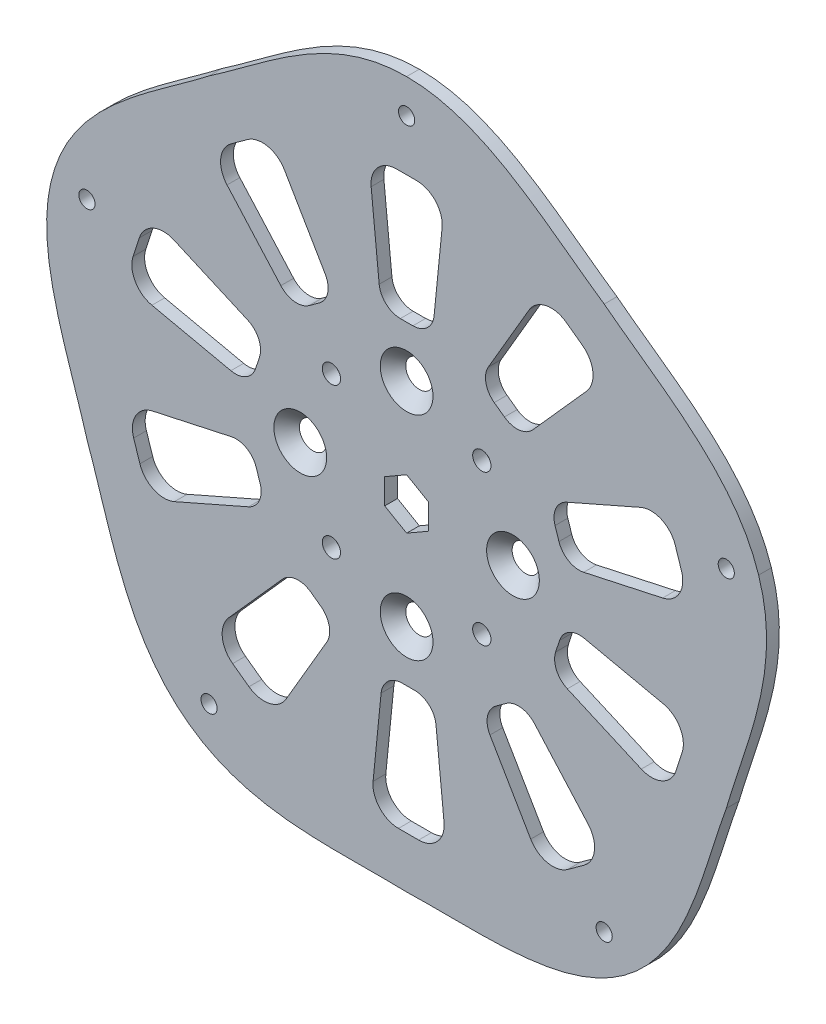
SolidWorks part; units mm, degrees
material "ABS"
ref_plane "Płaszczyzna przednia" through (0, 0, 0) normal (0, 0, 1) x (1, 0, 0)
ref_plane "Płaszczyzna górna" through (0, 0, 0) normal (0, 1, 0) x (1, 0, 0)
ref_plane "Płaszczyzna prawa" through (0, 0, 0) normal (1, 0, 0) x (0, 0, -1)
sketch "Szkic1" plane through (0, 0, 0) normal (0, 0, 1) x (1, 0, 0)
  line L0 (0, 0) -> (51.1373, 70.3845) construction
  line L1 (0, 0) -> (0, 87) construction
  line L2 (-1.4751, 37) -> (1.4751, 37)
  line L3 (-2.3701, 67) -> (2.3701, 67)
  line L4 (-6.4502, 41.5025) -> (-8.3403, 60.403)
  line L5 (6.4502, 41.5025) -> (8.3403, 60.403)
  line L6 (29.6563, 29.9183) -> (42.2948, 44.0981)
  line L7 (37.5075, 55.7306) -> (41.3424, 52.9445)
  line L8 (19.2195, 37.501) -> (28.7999, 53.9028)
  line L9 (20.5981, 30.9341) -> (22.9848, 29.2)
  line L10 (41.6213, 6.9063) -> (60.1808, 10.9493)
  line L11 (63.1452, 23.1741) -> (64.61, 18.6659)
  line L12 (37.6348, 19.1754) -> (55.0262, 26.8135)
  line L13 (34.8901, 13.0524) -> (35.8017, 10.2466)
  line L14 (37.7751, -18.7437) -> (55.1665, -26.3818)
  line L15 (64.7503, -18.2342) -> (63.2855, -22.7424)
  line L16 (41.7616, -6.4746) -> (60.321, -10.5176)
  line L17 (35.942, -9.8149) -> (35.0304, -12.6206)
  line L18 (19.5868, -37.2342) -> (29.1671, -53.6359)
  line L19 (41.7096, -52.6776) -> (37.8748, -55.4638)
  line L20 (30.0235, -29.6514) -> (42.662, -43.8313)
  line L21 (23.352, -28.9332) -> (20.9653, -30.6672)
  line L22 (-5.9963, -41.5025) -> (-7.8864, -60.403)
  line L23 (2.824, -67) -> (-1.9161, -67)
  line L24 (6.9042, -41.5025) -> (8.7942, -60.403)
  line L25 (1.929, -37) -> (-1.0211, -37)
  line L26 (-29.2023, -29.9183) -> (-41.8408, -44.0981)
  line L27 (-37.0536, -55.7306) -> (-40.8884, -52.9445)
  line L28 (-18.7656, -37.501) -> (-28.3459, -53.9028)
  line L29 (-20.1441, -30.9341) -> (-22.5308, -29.2)
  line L30 (-41.1673, -6.9063) -> (-59.7268, -10.9493)
  line L31 (-62.6913, -23.1741) -> (-64.1561, -18.6659)
  line L32 (-37.1809, -19.1754) -> (-54.5722, -26.8135)
  line L33 (-34.4362, -13.0524) -> (-35.3478, -10.2466)
  line L34 (-37.3211, 18.7437) -> (-54.7125, 26.3818)
  line L35 (-64.2963, 18.2342) -> (-62.8316, 22.7424)
  line L36 (-41.3076, 6.4746) -> (-59.8671, 10.5176)
  line L37 (-35.4881, 9.8149) -> (-34.5764, 12.6206)
  line L38 (-19.1328, 37.2342) -> (-28.7132, 53.6359)
  line L39 (-41.2557, 52.6776) -> (-37.4208, 55.4638)
  line L40 (-29.5696, 29.6514) -> (-42.2081, 43.8313)
  line L41 (-22.8981, 28.9332) -> (-20.5114, 30.6672)
  circle A0 centre (0, 0) radius 79 construction
  circle A2 centre (0, 0) radius 25 construction
  circle A3 centre (0, 0) radius 3.3
  circle A4 centre (0, 25) radius 3.2
  circle A5 centre (0, 79) radius 1.9
  circle A6 centre (25, 0) radius 3.2
  circle A7 centre (0, -25) radius 3.2
  circle A8 centre (-25, 0) radius 3.2
  circle A9 centre (75.1335, 24.4123) radius 1.9
  circle A10 centre (46.435, -63.9123) radius 1.9
  circle A11 centre (-46.435, -63.9123) radius 1.9
  circle A12 centre (-75.1335, 24.4123) radius 1.9
  circle A13 centre (0, 0) radius 87 construction
  arc A14 (8.3403, 60.403) -> (2.3701, 67) centre (2.3701, 61) ccw
  arc A15 (-2.3701, 67) -> (-8.3403, 60.403) centre (-2.3701, 61) ccw
  arc A16 (6.4502, 41.5025) -> (1.4751, 37) centre (1.4751, 42) cw
  arc A17 (-6.4502, 41.5025) -> (-1.4751, 37) centre (-1.4751, 42) ccw
  arc A18 (29.6563, 29.9183) -> (22.9848, 29.2) centre (25.9237, 33.2451) cw
  arc A19 (42.2948, 44.0981) -> (41.3424, 52.9445) centre (37.8157, 48.0904) ccw
  arc A20 (37.5075, 55.7306) -> (28.7999, 53.9028) centre (33.9808, 50.8765) ccw
  arc A21 (19.2195, 37.501) -> (20.5981, 30.9341) centre (23.537, 34.9791) ccw
  arc A22 (41.6213, 6.9063) -> (35.8017, 10.2466) centre (40.557, 11.7917) cw
  arc A23 (60.1808, 10.9493) -> (64.61, 18.6659) centre (58.9037, 16.8118) ccw
  arc A24 (63.1452, 23.1741) -> (55.0262, 26.8135) centre (57.4389, 21.32) ccw
  arc A25 (37.6348, 19.1754) -> (34.8901, 13.0524) centre (39.6454, 14.5974) ccw
  arc A26 (37.7751, -18.7437) -> (35.0304, -12.6206) centre (39.7857, -14.1657) cw
  arc A27 (55.1665, -26.3818) -> (63.2855, -22.7424) centre (57.5792, -20.8882) ccw
  arc A28 (64.7503, -18.2342) -> (60.321, -10.5176) centre (59.044, -16.3801) ccw
  arc A29 (41.7616, -6.4746) -> (35.942, -9.8149) centre (40.6973, -11.36) ccw
  arc A30 (19.5868, -37.2342) -> (20.9653, -30.6672) centre (23.9042, -34.7123) cw
  arc A31 (29.1671, -53.6359) -> (37.8748, -55.4638) centre (34.3481, -50.6097) ccw
  arc A32 (41.7096, -52.6776) -> (42.662, -43.8313) centre (38.1829, -47.8235) ccw
  arc A33 (30.0235, -29.6514) -> (23.352, -28.9332) centre (26.2909, -32.9783) ccw
  arc A34 (-5.9963, -41.5025) -> (-1.0211, -37) centre (-1.0211, -42) cw
  arc A35 (-7.8864, -60.403) -> (-1.9161, -67) centre (-1.9161, -61) ccw
  arc A36 (2.824, -67) -> (8.7942, -60.403) centre (2.824, -61) ccw
  arc A37 (6.9042, -41.5025) -> (1.929, -37) centre (1.929, -42) ccw
  arc A38 (-29.2023, -29.9183) -> (-22.5308, -29.2) centre (-25.4697, -33.2451) cw
  arc A39 (-41.8408, -44.0981) -> (-40.8884, -52.9445) centre (-37.3617, -48.0904) ccw
  arc A40 (-37.0536, -55.7306) -> (-28.3459, -53.9028) centre (-33.5269, -50.8765) ccw
  arc A41 (-18.7656, -37.501) -> (-20.1441, -30.9341) centre (-23.083, -34.9791) ccw
  arc A42 (-41.1673, -6.9063) -> (-35.3478, -10.2466) centre (-40.1031, -11.7917) cw
  arc A43 (-59.7268, -10.9493) -> (-64.1561, -18.6659) centre (-58.4497, -16.8118) ccw
  arc A44 (-62.6913, -23.1741) -> (-54.5722, -26.8135) centre (-56.9849, -21.32) ccw
  arc A45 (-37.1809, -19.1754) -> (-34.4362, -13.0524) centre (-39.1914, -14.5974) ccw
  arc A46 (-37.3211, 18.7437) -> (-34.5764, 12.6206) centre (-39.3317, 14.1657) cw
  arc A47 (-54.7125, 26.3818) -> (-62.8316, 22.7424) centre (-57.1252, 20.8882) ccw
  arc A48 (-64.2963, 18.2342) -> (-59.8671, 10.5176) centre (-58.59, 16.3801) ccw
  arc A49 (-41.3076, 6.4746) -> (-35.4881, 9.8149) centre (-40.2434, 11.36) ccw
  arc A50 (-19.1328, 37.2342) -> (-20.5114, 30.6672) centre (-23.4503, 34.7123) cw
  arc A51 (-28.7132, 53.6359) -> (-37.4208, 55.4638) centre (-33.8941, 50.6097) ccw
  arc A52 (-41.2557, 52.6776) -> (-42.2081, 43.8313) centre (-37.729, 47.8235) ccw
  arc A53 (-29.5696, 29.6514) -> (-22.8981, 28.9332) centre (-25.837, 32.9783) ccw
  spline S0 degree 3 poles (0, 87) (18.2248, 86.9986) (32.2889, 73.5369) (46.435, 63.9123) knots 0 0 0 0 1 1 1 1
  spline S1 degree 3 poles (82.7419, 26.8845) (77.1088, 44.2169) (59.9599, 53.4327) (46.435, 63.9123) knots 0 0 0 0 1 1 1 1
  spline S2 degree 3 poles (82.7419, 26.8845) (88.3724, 9.5512) (79.9156, -7.9844) (75.1335, -24.4123) knots 0 0 0 0 1 1 1 1
  spline S3 degree 3 poles (51.1373, -70.3845) (65.8807, -59.6711) (69.3462, -40.5137) (75.1335, -24.4123) knots 0 0 0 0 1 1 1 1
  spline S4 degree 3 poles (51.1373, -70.3845) (36.3923, -81.0957) (17.1016, -78.4715) (0, -79) knots 0 0 0 0 1 1 1 1
  spline S5 degree 3 poles (-51.1373, -70.3845) (-36.3923, -81.0957) (-17.1016, -78.4715) (0, -79) knots 0 0 0 0 1 1 1 1
  spline S6 degree 3 poles (-51.1373, -70.3845) (-65.8807, -59.6711) (-69.3462, -40.5137) (-75.1335, -24.4123) knots 0 0 0 0 1 1 1 1
  spline S7 degree 3 poles (-82.7419, 26.8845) (-88.3724, 9.5512) (-79.9156, -7.9844) (-75.1335, -24.4123) knots 0 0 0 0 1 1 1 1
  spline S8 degree 3 poles (-82.7419, 26.8845) (-77.1088, 44.2169) (-59.9599, 53.4327) (-46.435, 63.9123) knots 0 0 0 0 1 1 1 1
  spline S9 degree 3 poles (0, 87) (-18.2248, 86.9986) (-32.2889, 73.5369) (-46.435, 63.9123) knots 0 0 0 0 1 1 1 1
  point P18 (0, 0)
  point P27 (0, 0)
  point P43 (0, 37)
  point P64 (0, 0)
  point P65 (0, 67)
  point P67 (9, 67)
  point P70 (-9, 67)
  point P73 (6, 37)
  point P76 (-6, 37)
  point P188 (0.227, 0)
  dimension "D1" = 158
  dimension "D2" = 6.6
  dimension "D3" = 50
  dimension "D4" = 3.8
  dimension "D5" = 6.4
  dimension "D8" = 174
  dimension "D13" = 37
  dimension "D14" = 6
  dimension "D15" = 5
  dimension "D9" = 36
  dimension "D10" = 12
  dimension "D11" = 18
  dimension "D12" = 30
  dimension "D6" = 4
  dimension "D7" = 5
  dimension "D16" = 10
extrude "Dodanie-wyciągnięcie1" add sketch "Szkic1" along normal blind 3 contours S0 S9 S8 S7 S6 S5 S4 S3 S2 S1 A3 A4 A5 A6 A7 A8 A9 A10 A11 A12 A17 L4 A15 L3 A14 L5 A16 L2 A21 L8 A20 L7 A19 L6 A18 L9 A25 L12 region at (23.5794, 77.0008, 0)
sketch "Sketch1" plane through (0, 0, 0) normal (0, 0, -1) x (-1, 0, 0)
  line L0 (0, 0) -> (-16.4631, 16.4631) construction
  line L1 (0, 0) -> (14.4362, 0) construction
  circle A0 centre (0, 0) radius 25 construction
  circle A1 centre (-17.6777, 17.6777) radius 2.15
  circle A2 centre (17.6777, 17.6777) radius 2.15
  circle A3 centre (17.6777, -17.6777) radius 2.15
  circle A4 centre (-17.6777, -17.6777) radius 2.15
  point P17 (0, 0)
  dimension "D1" = 135
  dimension "D2" = 4.3
  dimension "D3" = 4
extrude "Cut-Extrude1" cut sketch "Sketch1" against normal blind 7
chamfer "Chamfer1" distance 3 angle 45 4 edges at (28.2, 0, 3) (-21.8, 0, 3) (3.2, 25, 3) (3.2, -25, 3)
sketch "Sketch2" plane through (0, 0, 3) normal (0, 0, 1) x (1, 0, 0)
  line L1 (-5.15, 2.9734) -> (-5.15, -2.9734)
  line L2 (-5.15, -2.9734) -> (0, -5.9467)
  line L3 (0, -5.9467) -> (5.15, -2.9734)
  line L4 (5.15, -2.9734) -> (5.15, 2.9734)
  line L5 (5.15, 2.9734) -> (0, 5.9467)
  line L6 (0, 5.9467) -> (-5.15, 2.9734)
  circle A0 centre (0, 0) radius 5.15 construction
  dimension "D1" = 10.3
extrude "Cut-Extrude2" cut sketch "Sketch2" against normal blind 5.5
